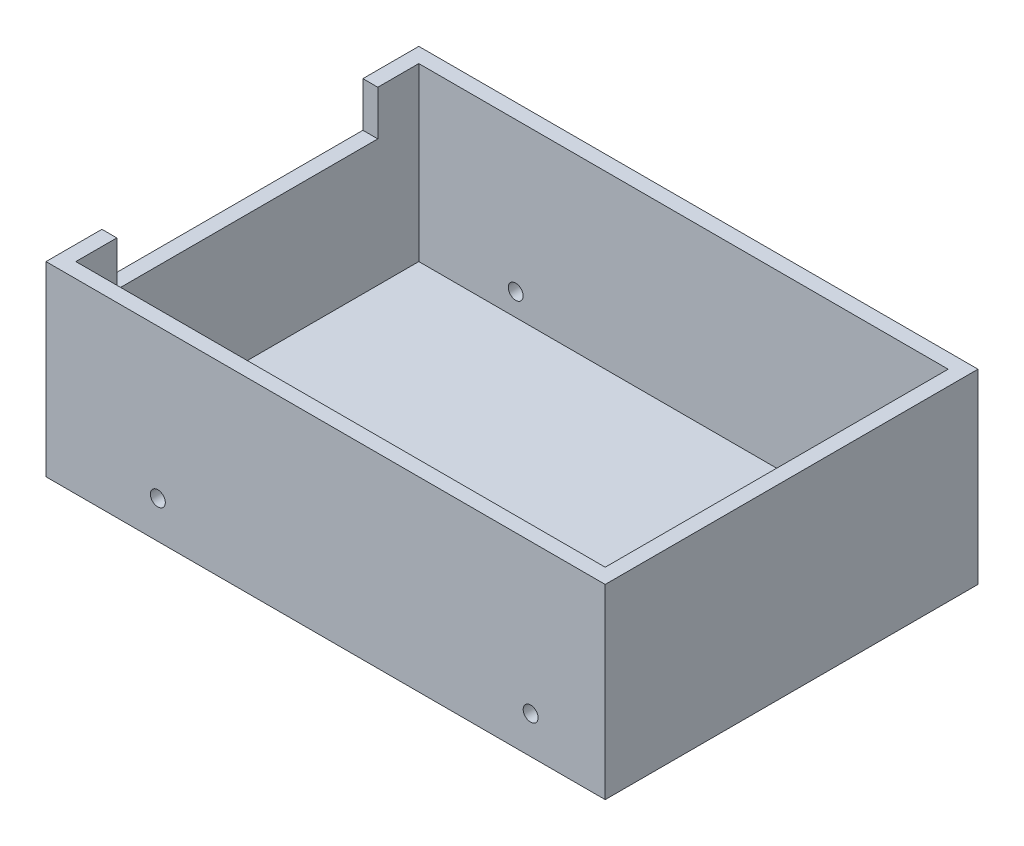
SolidWorks part; units mm, degrees
ref_plane "Front Plane" through (0, 0, 0) normal (0, 0, 1) x (1, 0, 0)
ref_plane "Top Plane" through (0, 0, 0) normal (0, 1, 0) x (1, 0, 0)
ref_plane "Right Plane" through (0, 0, 0) normal (1, 0, 0) x (0, 0, -1)
sketch "Sketch2" plane through (0, 0, 0) normal (0, 1, 0) x (1, 0, 0)
  line L1 (187.5, -125) -> (-187.5, -125)
  line L2 (187.5, -125) -> (187.5, 125)
  line L3 (187.5, 125) -> (-187.5, 125)
  line L4 (-187.5, -125) -> (-187.5, 125)
  line L5 (187.5, -125) -> (-187.5, 125) construction
  line L6 (187.5, 125) -> (-187.5, -125) construction
  point P0 (0, 0)
  dimension "D1" = 250
  dimension "D2" = 375
extrude "Boss-Extrude1" add sketch "Sketch2" along normal blind 125
shell "Shell1" thickness 10 removed face at (0, 125, 0)
sketch "Sketch3" plane through (0, 0, 0) normal (0, 0, 1) x (1, 0, 0)
  line L0 (187.5, 125) -> (187.5, 0) construction
  line L1 (-187.5, 125) -> (-187.5, 0) construction
  line L2 (-187.5, 0) -> (187.5, 0) construction
  circle A0 centre (137.5, 25) radius 5
  circle A1 centre (-112.5, 25) radius 5
  point P4 (0, 0)
  dimension "D1" = 50
  dimension "D2" = 250
  dimension "D3" = 75
  dimension "D4" = 25
  dimension "D5" = 10
extrude "Cut-Extrude1" cut sketch "Sketch3" against normal through all both and the other way through all
sketch "Sketch4" plane through (-187.5, 0, 0) normal (-1, 0, 0) x (0, 0, 1)
  line L0 (-125, 125) -> (125, 125) construction
  line L1 (-87.5, 125) -> (87.5, 125)
  line L2 (-87.5, 125) -> (-87.5, 95)
  line L3 (-87.5, 95) -> (87.5, 95)
  line L4 (87.5, 125) -> (87.5, 95)
  line L5 (-87.5, 125) -> (87.5, 95) construction
  line L6 (-87.5, 95) -> (87.5, 125) construction
  point P4 (0, 110)
  point P7 (0, 0)
  dimension "D1" = 175
  dimension "D2" = 30
extrude "Cut-Extrude2" cut sketch "Sketch4" against normal up to next and the other way through all
